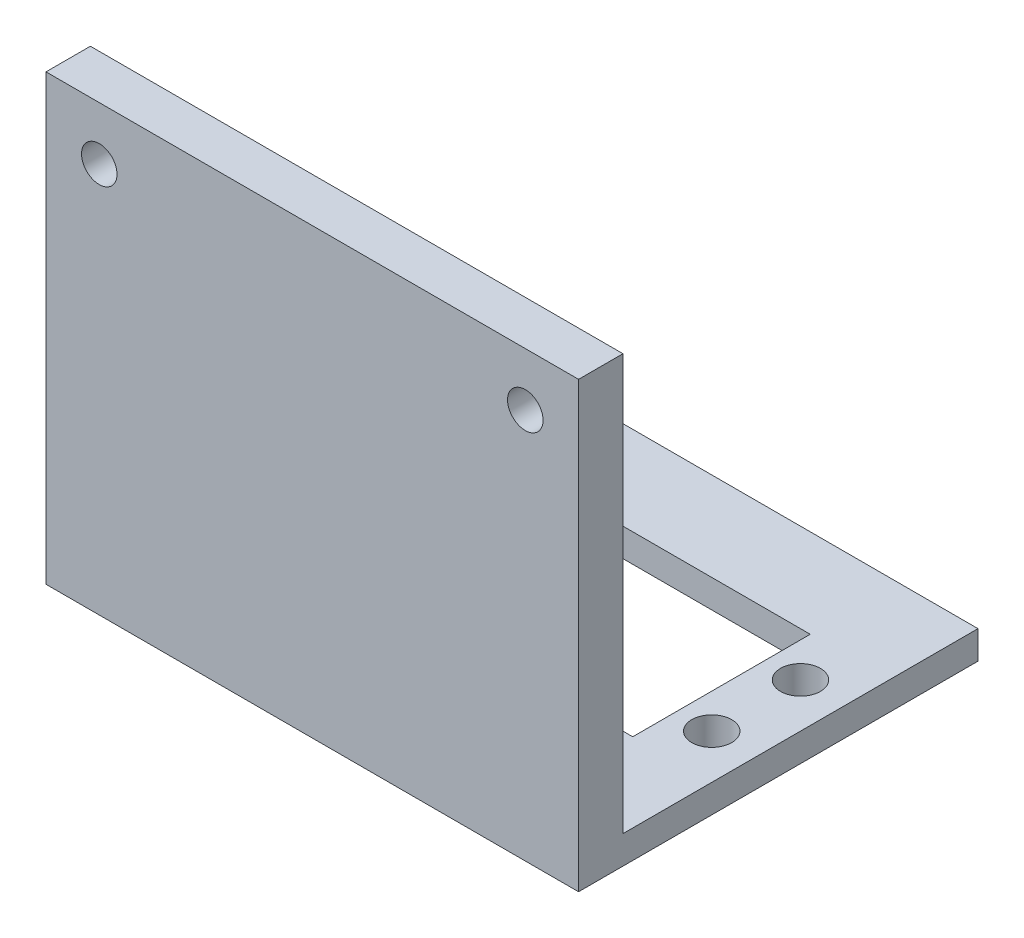
SolidWorks part; units mm, degrees
ref_plane "Front Plane" through (0, 0, 0) normal (0, 0, 1) x (1, 0, 0)
ref_plane "Top Plane" through (0, 0, 0) normal (0, 1, 0) x (1, 0, 0)
ref_plane "Right Plane" through (0, 0, 0) normal (1, 0, 0) x (0, 0, -1)
sketch "Sketch1" plane through (0, 0, 0) normal (0, 1, 0) x (1, 0, 0)
  line L1 (30, -20) -> (-30, -20)
  line L2 (30, -20) -> (30, 20)
  line L3 (30, 20) -> (-30, 20)
  line L4 (-30, -20) -> (-30, 20)
  line L5 (30, -20) -> (-30, 20) construction
  line L6 (30, 20) -> (-30, -20) construction
  line L11 (25, -5) -> (-23.8, -5) construction
  line L12 (25, -5) -> (25, 5) construction
  line L13 (25, 5) -> (-23.8, 5) construction
  line L14 (-23.8, -5) -> (-23.8, 5) construction
  line L15 (25, -5) -> (-23.8, 5) construction
  line L16 (25, 5) -> (-23.8, -5) construction
  line L17 (21.1, -10) -> (-19.9, -10)
  line L18 (21.1, -10) -> (21.1, 10)
  line L19 (21.1, 10) -> (-19.9, 10)
  line L20 (-19.9, -10) -> (-19.9, 10)
  line L21 (21.1, -10) -> (-19.9, 10) construction
  line L22 (21.1, 10) -> (-19.9, -10) construction
  circle A0 centre (25, 5) radius 2.25
  circle A1 centre (-23.8, 5) radius 2.25
  circle A2 centre (-23.8, -5) radius 2.25
  circle A3 centre (25, -5) radius 2.25
  point P0 (0, 0)
  point P6 (0, 0)
  point P7 (0.6, 0)
  point P16 (25, 0)
  point P17 (0.6, 0)
  dimension "D5" = 4.5
  dimension "D1" = 60
  dimension "D2" = 40
  dimension "D3" = 48.8
  dimension "D4" = 10
  dimension "D6" = 5
  dimension "D7" = 20
  dimension "D8" = 41
extrude "Boss-Extrude1" add sketch "Sketch1" along normal blind 3.175
sketch "Sketch2" plane through (0, 0, 20) normal (0, 0, 1) x (1, 0, 0)
  line L0 (30, 3.175) -> (30, 0) construction
  line L1 (-30, 0) -> (30, 0)
  line L2 (-30, 0) -> (-30, 50)
  line L3 (-30, 50) -> (30, 50)
  line L4 (30, 0) -> (30, 50)
  dimension "D1" = 50
extrude "Boss-Extrude2" add sketch "Sketch2" along normal blind 5
sketch "Sketch3" plane through (0, 0, 20) normal (0, 0, -1) x (-1, 0, 0)
  line L0 (0, 0) -> (0, 50) construction
  line L1 (-30, 0) -> (30, 0) construction
  line L2 (-30, 50) -> (30, 50) construction
  line L3 (-30, 3.175) -> (-30, 50) construction
  point P0 (-24, 44)
  point P1 (24, 44)
  point P2 (0, 0)
  dimension "D1" = 6
  dimension "D2" = 6
hole_wizard "Ø4.0mm Dowel Hole1" positions "Sketch4" profile "Sketch5" hole size "Ø4.0" standard "ANSI Metric" end condition through all
sketch "Sketch4" plane through (0, 0, 20) normal (0, 0, -1) x (-1, 0, 0)
  point P0 (-24, 44)
  point P3 (24, 44)
sketch "Sketch5" plane through (24, 44, 20) normal (1, 0, 0) x (0, 1, 0)
  line L0 (0, 0) -> (0, 5)
  line L1 (0, 5) -> (2, 5)
  line L2 (2, 5) -> (2, 0)
  line L5 (2, 0) -> (0, 0)
  line L11 (0, -6.35) -> (0, 107.95) construction
  dimension "Thru Hole Dia." = 4
  dimension "Thru Hole Depth" = 5
